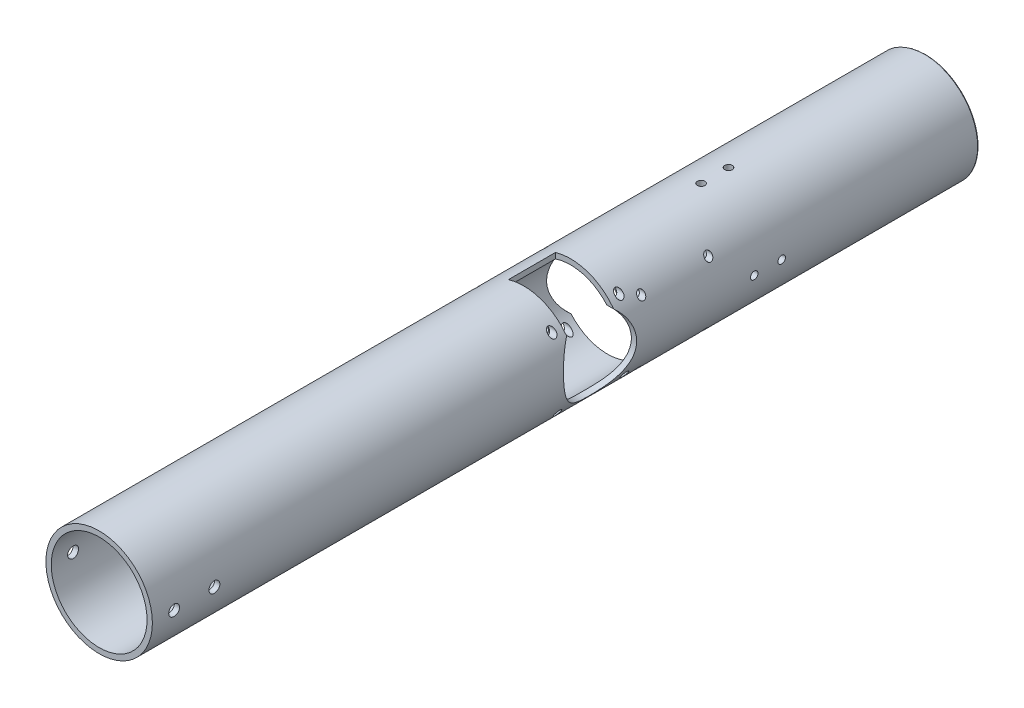
SolidWorks part; units mm, degrees
material "6061 Alloy"
ref_plane "Front Plane" through (0, 0, 0) normal (0, 0, 1) x (1, 0, 0)
ref_plane "Top Plane" through (0, 0, 0) normal (0, 1, 0) x (1, 0, 0)
ref_plane "Right Plane" through (0, 0, 0) normal (1, 0, 0) x (0, 0, -1)
sketch "Sketch1" plane through (0, 0, 0) normal (0, 0, 1) x (1, 0, 0)
  circle A0 centre (0, 0) radius 31.75
  circle A1 centre (0, 0) radius 28.575
  dimension "D1" = 63.5
  dimension "D2" = 57.15
extrude "Boss-Extrude1" add sketch "Sketch1" along normal blind 125 and the other way blind 250 contours A1 | A0
sketch "Sketch2" plane through (0, 0, 0) normal (1, 0, 0) x (0, 0, -1)
  circle A2 centre (73.488, -2) radius 21.75
  dimension "D1" = 43.5
  dimension "D2" = 73.488
  dimension "D3" = 2
extrude "Cut-Extrude1" cut sketch "Sketch2" against normal through all
sketch "Sketch3" plane through (0, 0, 0) normal (1, 0, 0) x (0, 0, -1)
  circle A1 centre (23.45, 2) radius 21.75
  dimension "D1" = 23.45
  dimension "D2" = 43.5
  dimension "D3" = 2
extrude "Cut-Extrude2" cut sketch "Sketch3" along normal through all
sketch "Sketch5" plane through (0, 0, 0) normal (1, 0, 0) x (0, 0, -1)
  line L1 (87.488, -12.75) -> (59.488, -12.75)
  line L2 (87.488, -12.75) -> (87.488, -34.75)
  line L3 (87.488, -34.75) -> (59.488, -34.75)
  line L4 (59.488, -12.75) -> (59.488, -34.75)
  line L5 (87.488, -12.75) -> (59.488, -34.75) construction
  line L6 (87.488, -34.75) -> (59.488, -12.75) construction
  circle A0 centre (73.488, -2) radius 21.75 construction
  circle A1 centre (73.488, -2) radius 21.75 construction
  circle A2 centre (73.488, -2) radius 21.75 construction
  point P0 (73.488, -23.75)
  dimension "D1" = 28
  dimension "D2" = 22
extrude "Cut-Extrude4" cut sketch "Sketch5" against normal through all from offset 9
sketch "Sketch6" plane through (0, 0, 0) normal (1, 0, 0) x (0, 0, -1)
  line L1 (9.45, 34.75) -> (37.45, 34.75)
  line L2 (9.45, 34.75) -> (9.45, 12.75)
  line L3 (9.45, 12.75) -> (37.45, 12.75)
  line L4 (37.45, 34.75) -> (37.45, 12.75)
  line L5 (9.45, 34.75) -> (37.45, 12.75) construction
  line L6 (9.45, 12.75) -> (37.45, 34.75) construction
  circle A0 centre (23.45, 2) radius 21.75 construction
  circle A1 centre (23.45, 2) radius 21.75 construction
  circle A2 centre (23.45, 2) radius 21.75 construction
  point P0 (23.45, 23.75)
  dimension "D1" = 28
  dimension "D2" = 22
extrude "Cut-Extrude5" cut sketch "Sketch6" along normal through all from offset 9 offset against normal yes
sketch "Sketch10" plane through (0, 0, 0) normal (1, 0, 0) x (0, 0, -1)
  line L1 (113.488, 38) -> (33.488, 38)
  line L2 (113.488, 38) -> (113.488, -42)
  line L3 (113.488, -42) -> (33.488, -42)
  line L4 (33.488, 38) -> (33.488, -42)
  line L5 (113.488, 38) -> (33.488, -42) construction
  line L6 (113.488, -42) -> (33.488, 38) construction
  point P0 (73.488, -2)
  dimension "D1" = 80
  dimension "D2" = 80
sketch "Sketch11" plane through (0, 0, 0) normal (1, 0, 0) x (0, 0, -1)
  line L0 (113.488, 38) -> (33.488, -42) construction
  line L1 (113.488, -42) -> (33.488, 38) construction
  line L2 (51.738, -2) -> (95.238, -2) construction
  line L3 (53.488, 18) -> (53.488, -22) construction
  circle A0 centre (93.488, 18) radius 2
  circle A1 centre (53.488, 18) radius 2
  circle A2 centre (53.488, -22) radius 2
  circle A3 centre (93.488, -22) radius 2
  arc A4 (87.488, -18.6452) -> (59.488, -18.6452) centre (73.488, -2) ccw construction
  arc A5 (87.488, -18.6452) -> (59.488, -18.6452) centre (73.488, -2) ccw construction
  point P18 (53.488, -2)
  dimension "D5" = 4
  dimension "D1" = 40
extrude "Cut-Extrude8" cut sketch "Sketch11" against normal through all both and the other way through all
sketch "Sketch12" plane through (0, 0, 0) normal (1, 0, 0) x (0, 0, -1)
  line L0 (-125, 31.75) -> (-125, -31.75) construction
  circle A0 centre (-112, 0) radius 3.25
  circle A1 centre (-88, 0) radius 3.25
  dimension "D2" = 6.5
  dimension "D3" = 24
  dimension "D4" = 13
extrude "Cut-Extrude10" cut sketch "Sketch12" against normal through all both and the other way through all
sketch "Sketch13" plane through (0, 0, 0) normal (0, 1, 0) x (1, 0, 0)
  line L0 (0, -34.925) -> (0, 34.925) construction
  line L1 (28.575, 250) -> (-28.575, 250) construction
  line L2 (0, 250) -> (0, -125) construction
  circle A0 centre (0, 238) radius 2.25 construction
  circle A1 centre (0, 205.9) radius 2.25 construction
  dimension "D2" = 4.5
  dimension "D3" = 32.1
  dimension "D1" = 12
sketch "Sketch14" plane through (0, 0, 0) normal (1, 0, 0) x (0, 0, -1)
  line L0 (3.45, -18) -> (3.45, 22) construction
  line L1 (-1.55, 27) -> (48.45, 27) construction
  line L2 (-1.55, 27) -> (-1.55, -23) construction
  line L3 (-1.55, -23) -> (48.45, -23) construction
  line L4 (48.45, 27) -> (48.45, -23) construction
  line L5 (-1.55, 27) -> (48.45, -23) construction
  line L6 (-1.55, -23) -> (48.45, 27) construction
  circle A0 centre (3.45, 22) radius 2
  circle A1 centre (43.45, 22) radius 2
  circle A2 centre (43.45, -18) radius 2
  circle A3 centre (3.45, -18) radius 2
  point P0 (23.45, 2)
  point P14 (3.45, 2)
  dimension "D5" = 4
  dimension "D1" = 40
  dimension "D2" = 50
sketch "Sketch15" plane through (0, 0, 0) normal (1, 0, 0) x (0, 0, -1)
  circle A0 centre (3.45, 22) radius 2
  circle A1 centre (43.45, 22) radius 2
  circle A2 centre (43.45, -18) radius 2
  circle A3 centre (3.45, -18) radius 2
  dimension "D1" = 4
extrude "Cut-Extrude12" cut sketch "Sketch15" against normal through all and the other way through all
hole_wizard "M4 Clearance Hole1" positions "Sketch18" profile "Sketch19" hole size "M4" standard "ANSI Metric"
sketch "Sketch18" plane through (0, 0, 0) normal (1, 0, 0) x (0, 0, -1)
  circle A0 centre (3.45, 22) radius 2 construction
  circle A1 centre (43.45, 22) radius 2 construction
  circle A2 centre (3.45, -18) radius 2 construction
  circle A3 centre (43.45, -18) radius 2 construction
  point P0 (3.45, 22)
  point P2 (43.45, 22)
  point P4 (3.45, -18)
  point P6 (43.45, -18)
  point P20 (93.488, 18)
  point P23 (53.488, 18)
  point P26 (93.488, -22)
  point P29 (53.488, -22)
sketch "Sketch19" plane through (0, 22, -3.45) normal (0, 1, 0) x (0, 0, 1)
  line L0 (0, 0) -> (0, 31.75)
  line L1 (0, 31.75) -> (2.25, 31.75)
  line L2 (2.25, 31.75) -> (2.25, 0)
  line L5 (2.25, 0) -> (0, 0)
  line L11 (0, -6.35) -> (0, 107.95) construction
  dimension "Thru Hole Dia." = 4.5
  dimension "Thru Hole Depth" = 31.75
mirror "Mirror1" about plane through (0, 0, 0) normal (1, 0, 0) of "M4 Clearance Hole1"
sketch "Sketch21" plane through (0, 0, -250) normal (0, 0, -1) x (-1, 0, 0)
  circle A0 centre (0, 0) radius 30
  dimension "D1" = 60
extrude "Cut-Extrude14" cut sketch "Sketch21" against normal blind 7
sketch "Sketch22" plane through (0, 0, 0) normal (1, 0, 0) x (0, 0, -1)
  line L0 (250, -31.75) -> (250, 31.75) construction
  line L1 (250, -31.75) -> (250, 31.75) construction
  circle A0 centre (221.65, 0) radius 2.25 construction
  circle A1 centre (131.65, 0) radius 2.25
  circle A2 centre (115.3, 0) radius 2.25
  circle A4 centre (238, 0) radius 2.25 construction
  point P14 (250, 0)
  dimension "D1" = 134.7
  dimension "D4" = 12
  dimension "D5" = 4.5
  dimension "D2" = 118.35
  dimension "D3" = 28.35
extrude "Cut-Extrude15" cut sketch "Sketch22" along normal through all
pattern_circular "CirPattern2" count 4 over 360 about axis through (0, 0, -250) along (0, 0, 1) of "Cut-Extrude15"
sketch "Sketch23" plane through (0, 0, -243) normal (0, 0, -1) x (-1, 0, 0)
  circle A0 centre (0, 0) radius 28.575 construction
  circle A1 centre (0, 0) radius 30
  circle A2 centre (0, 0) radius 30
  circle A3 centre (0, 0) radius 28.575
  dimension "D1" = 0
extrude "Boss-Extrude2" add sketch "Sketch23" along normal up to surface (7 mm away) up to face at (-30, 0, -250)
ref_plane "Plane1" through (0, 0, 75) normal (0, 0, 1) x (1, 0, 0)
split "Split1" trim tools "Plane1" bodies to split 124 resulting bodies 125 126
move or copy body "Body-Move/Copy1" bodies to move or copy 125 copy no translate (0, 0, 118.65) parameters "D1"=0, "D2"=0, "D3"=118.65
sketch "Sketch24" plane through (0, 0, 75) normal (0, 0, 1) x (1, 0, 0)
  circle A0 centre (0, 0) radius 28.575 construction
  circle A1 centre (0, 0) radius 31.75
  circle A2 centre (0, 0) radius 31.75
  circle A3 centre (0, 0) radius 28.575
  dimension "D1" = 0
extrude "Boss-Extrude3" add sketch "Sketch24" along normal up to surface (118.65 mm away) up to face at (31.75, 0, 193.65)
sketch "Sketch25" plane through (0, 0, -250) normal (0, 0, -1) x (-1, 0, 0)
  circle A0 centre (0, 0) radius 31.75 construction
  circle A1 centre (0, 0) radius 31.75
extrude "Cut-Extrude16" cut sketch "Sketch25" against normal blind 1
fillet "Fillet1" radius 0.5 2 edges at (-28.575, 0, -249) (-31.75, 0, -249)
